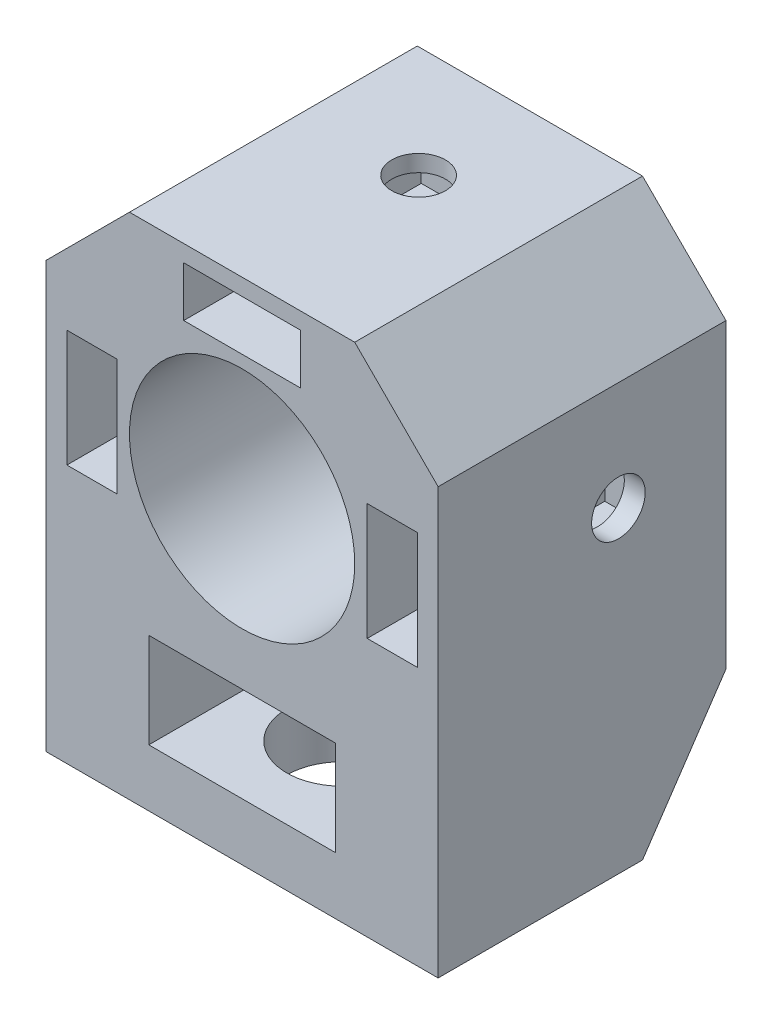
SolidWorks part; units mm, degrees
ref_plane "Front Plane" through (0, 0, 0) normal (0, 0, 1) x (1, 0, 0)
ref_plane "Top Plane" through (0, 0, 0) normal (0, 1, 0) x (1, 0, 0)
ref_plane "Right Plane" through (0, 0, 0) normal (1, 0, 0) x (0, 0, -1)
sketch "Sketch1" plane through (0, 0, 0) normal (0, 0, 1) x (1, 0, 0)
  line L1 (-11.938, -11.684) -> (11.938, -11.684)
  line L2 (-11.938, -11.684) -> (-11.938, 11.684)
  line L3 (-11.938, 11.684) -> (11.938, 11.684)
  line L4 (11.938, -11.684) -> (11.938, 11.684)
  line L5 (-11.938, -11.684) -> (11.938, 11.684) construction
  line L6 (-11.938, 11.684) -> (11.938, -11.684) construction
  point P0 (0, 0)
  dimension "D1" = 23.368
  dimension "D2" = 23.876
extrude "Boss-Extrude1" add sketch "Sketch1" along normal blind 17.526
sketch "Sketch2" plane through (0, 0, 17.526) normal (0, 0, 1) x (1, 0, 0)
  circle A0 centre (0, 0) radius 6.858
  dimension "D1" = 13.716
extrude "Cut-Extrude2" cut sketch "Sketch2" against normal offset from surface (15.748 mm away) 1.778 up to face at (0, 0, 0)
sketch "Sketch3" plane through (0, 0, 1.778) normal (0, 0, 1) x (1, 0, 0)
  circle A0 centre (0, 0) radius 5.08
  circle A1 centre (0, 0) radius 6.858 construction
  dimension "D1" = 1.778
extrude "Cut-Extrude3" cut sketch "Sketch3" against normal blind 1.778
sketch "Sketch4" plane through (0, -11.684, 0) normal (0, -1, 0) x (1, 0, 0)
  line L1 (-11.938, 0) -> (11.938, 0)
  line L2 (-11.938, 0) -> (-11.938, 17.526)
  line L3 (-11.938, 17.526) -> (11.938, 17.526)
  line L4 (11.938, 0) -> (11.938, 17.526)
  line L5 (-11.938, 0) -> (11.938, 17.526) construction
  line L6 (-11.938, 17.526) -> (11.938, 0) construction
  line L7 (11.938, 17.526) -> (11.938, 0) construction
  line L8 (-11.938, 17.526) -> (-11.938, 0) construction
  point P0 (0, 8.763)
  dimension "D1" = 17.526
  dimension "D2" = 0
  dimension "D3" = 0
extrude "Boss-Extrude2" add sketch "Sketch4" along normal blind 7.62
sketch "Sketch6" plane through (0, 0, 17.526) normal (0, 0, 1) x (1, 0, 0)
  line L1 (-5.6813, -15.8192) -> (5.6813, -15.8192)
  line L2 (-5.6813, -15.8192) -> (-5.6813, -10.0416)
  line L3 (-5.6813, -10.0416) -> (5.6813, -10.0416)
  line L4 (5.6813, -15.8192) -> (5.6813, -10.0416)
  line L5 (-5.6813, -15.8192) -> (5.6813, -10.0416) construction
  line L6 (-5.6813, -10.0416) -> (5.6813, -15.8192) construction
  point P0 (0, -12.9304)
  dimension "D1" = 11.3627
  dimension "D2" = 5.7776
extrude "Cut-Extrude5" cut sketch "Sketch6" against normal through all
chamfer "Chamfer1" distance 5.08 angle 56 1 edges at (0, -19.304, 0) first distance on face at (0, -19.304, 8.763)
hole_wizard "1/4 Clearance Hole1" positions "Sketch8" profile "Sketch7" hole size "1/4" standard "ANSI Inch" end condition up to next
sketch "Sketch8" plane through (0, -19.304, 0) normal (0, -1, 0) x (-1, 0, 0)
  point P0 (0, -11.43)
  dimension "D1" = 11.43
sketch "Sketch7" plane through (0, -19.304, 11.43) normal (1, 0, 0) x (0, 0, -1)
  line L0 (0, 0) -> (0, 3.4848)
  line L1 (0, 3.4848) -> (3.3782, 3.4848)
  line L2 (3.3782, 3.4848) -> (3.3782, 0)
  line L5 (3.3782, 0) -> (0, 0)
  line L11 (0, -6.35) -> (0, 107.95) construction
  dimension "Thru Hole Dia." = 6.7564
  dimension "Thru Hole Depth" = 3.4848
sketch "Sketch10" plane through (0, 0, 17.526) normal (0, 0, 1) x (1, 0, 0)
  line L1 (-3.556, 7.62) -> (3.556, 7.62)
  line L2 (-3.556, 7.62) -> (-3.556, 10.668)
  line L3 (-3.556, 10.668) -> (3.556, 10.668)
  line L4 (3.556, 7.62) -> (3.556, 10.668)
  line L5 (-3.556, 7.62) -> (3.556, 10.668) construction
  line L6 (-3.556, 10.668) -> (3.556, 7.62) construction
  line L7 (7.62, -3.556) -> (10.668, -3.556)
  line L8 (7.62, -3.556) -> (7.62, 3.556)
  line L9 (7.62, 3.556) -> (10.668, 3.556)
  line L10 (10.668, -3.556) -> (10.668, 3.556)
  line L11 (7.62, -3.556) -> (10.668, 3.556) construction
  line L12 (7.62, 3.556) -> (10.668, -3.556) construction
  line L13 (-10.668, -3.556) -> (-7.62, -3.556)
  line L14 (-10.668, -3.556) -> (-10.668, 3.556)
  line L15 (-10.668, 3.556) -> (-7.62, 3.556)
  line L16 (-7.62, -3.556) -> (-7.62, 3.556)
  line L17 (-10.668, -3.556) -> (-7.62, 3.556) construction
  line L18 (-10.668, 3.556) -> (-7.62, -3.556) construction
  point P0 (0, 9.144)
  point P5 (9.144, 0)
  point P10 (-9.144, 0)
  dimension "D1" = 7.62
  dimension "D2" = 7.112
  dimension "D3" = 3.048
  dimension "D4" = 7.112
  dimension "D5" = 3.048
  dimension "D6" = 7.62
  dimension "D7" = 3.048
  dimension "D8" = 7.112
  dimension "D9" = 7.62
extrude "Cut-Extrude6" cut sketch "Sketch10" against normal blind 14.4653
hole_wizard "#4 Clearance Hole1" positions "Sketch12" profile "Sketch11" hole size "#4" standard "ANSI Inch"
sketch "Sketch12" plane through (0, 11.684, 0) normal (0, 1, 0) x (1, 0, 0)
  point P0 (0, -6.7779)
sketch "Sketch11" plane through (0, 11.684, 6.7779) normal (1, 0, 0) x (0, 0, 1)
  line L0 (0, 0) -> (0, 7.5846)
  line L1 (0, 7.5846) -> (1.6319, 6.604)
  line L2 (1.6319, 6.604) -> (1.6319, 0)
  line L5 (1.6319, 0) -> (0, 0)
  line L10 (0, 7.5846) -> (-1.632, 6.604) construction
  line L11 (0, -6.35) -> (0, 107.95) construction
  dimension "Hole Dia." = 3.2639
  dimension "Hole Depth" = 6.604
  dimension "Drill Angle" = 118
hole_wizard "#4 Clearance Hole2" positions "Sketch14" profile "Sketch13" hole size "#4" standard "ANSI Inch" end condition through all
sketch "Sketch14" plane through (11.938, 0, 0) normal (1, 0, 0) x (0, 0, -1)
  point P0 (-6.5482, 0)
sketch "Sketch13" plane through (11.938, 0, 6.5482) normal (0, 1, 0) x (0, 0, -1)
  line L0 (0, 0) -> (0, 23.876)
  line L1 (0, 23.876) -> (1.6319, 23.876)
  line L2 (1.6319, 23.876) -> (1.6319, 0)
  line L5 (1.6319, 0) -> (0, 0)
  line L11 (0, -6.35) -> (0, 107.95) construction
  dimension "Thru Hole Dia." = 3.2639
  dimension "Thru Hole Depth" = 23.876
mirror "Mirror1" about plane through (0, 0, 0) normal (1, 0, 0) of "#4 Clearance Hole2"
chamfer "Chamfer2" distance 5.08 angle 45 2 edges at (-11.938, 11.684, 8.763) (11.938, 11.684, 8.763)
